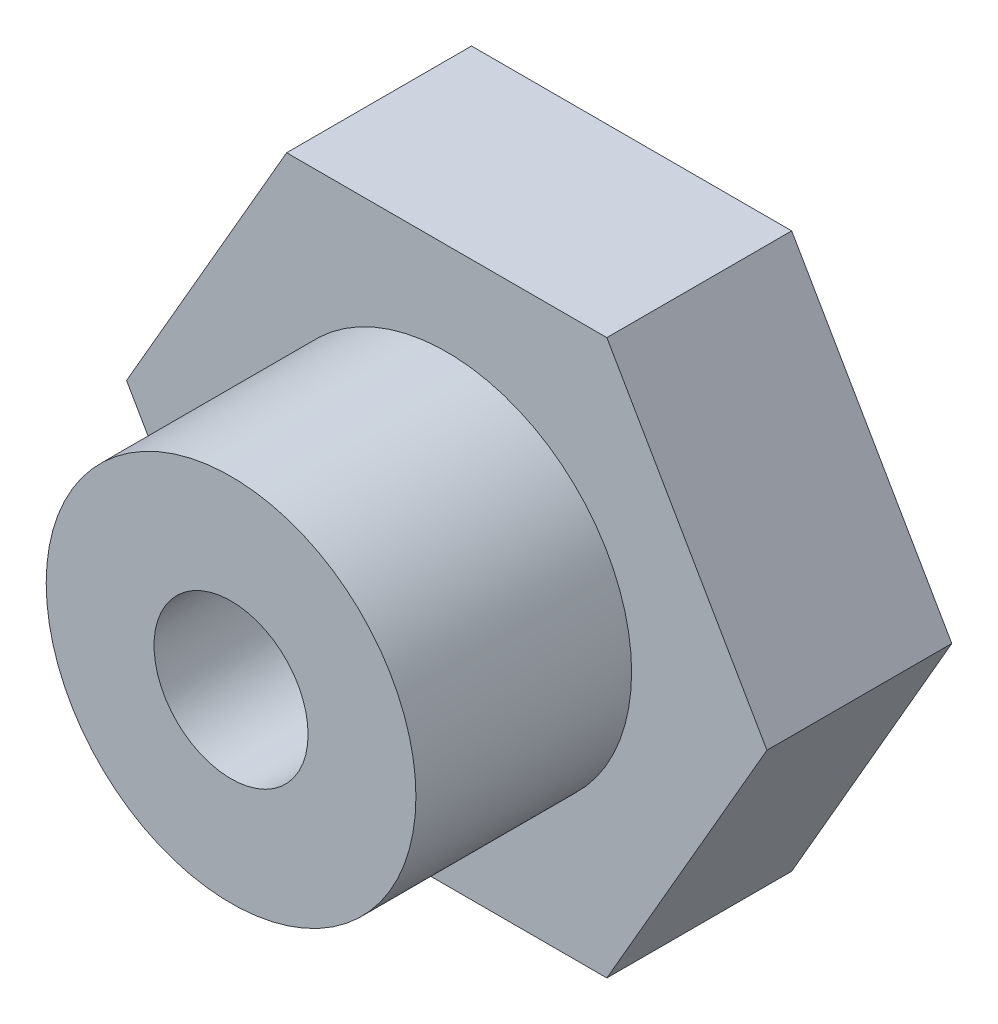
SolidWorks part; units mm, degrees
material "Aluminum Bronze"
ref_plane "Front Plane" through (0, 0, 0) normal (0, 0, 1) x (1, 0, 0)
ref_plane "Top Plane" through (0, 0, 0) normal (0, 1, 0) x (1, 0, 0)
ref_plane "Right Plane" through (0, 0, 0) normal (1, 0, 0) x (0, 0, -1)
sketch "Sketch1" plane through (0, 0, 0) normal (0, 0, 1) x (1, 0, 0)
  line L2 (10.3923, 0) -> (5.1962, 9)
  line L3 (5.1962, 9) -> (-5.1962, 9)
  line L4 (-5.1962, 9) -> (-10.3923, 0)
  line L5 (-10.3923, 0) -> (-5.1962, -9)
  line L6 (-5.1962, -9) -> (5.1962, -9)
  line L7 (5.1962, -9) -> (10.3923, 0)
  circle A0 centre (0, 0) radius 9 construction
  circle A1 centre (0, 0) radius 6
  circle A2 centre (0, 0) radius 2.5
  dimension "D1" = 12
  dimension "D2" = 5
  dimension "18" = 18
extrude "Boss-Extrude1" add sketch "Sketch1" against normal blind 6 contours L6 L7 L2 L3 L4 L5 A1 | A1 A2 region at (7.5561, -4.3625, 0) region at (-5.8303, 0, 0)
extrude "Boss-Extrude2" add sketch "Sketch1<3>" along normal blind 7 contours A1 A2 region at (-5.8303, 0, 0)
sketch "Sketch1<3>" plane through (0, 0, 0) normal (0, 0, 1) x (1, 0, 0) same geometry as "Sketch1"
cosmetic thread "Cosmetic Thread1" parameters "D2"=10.072
